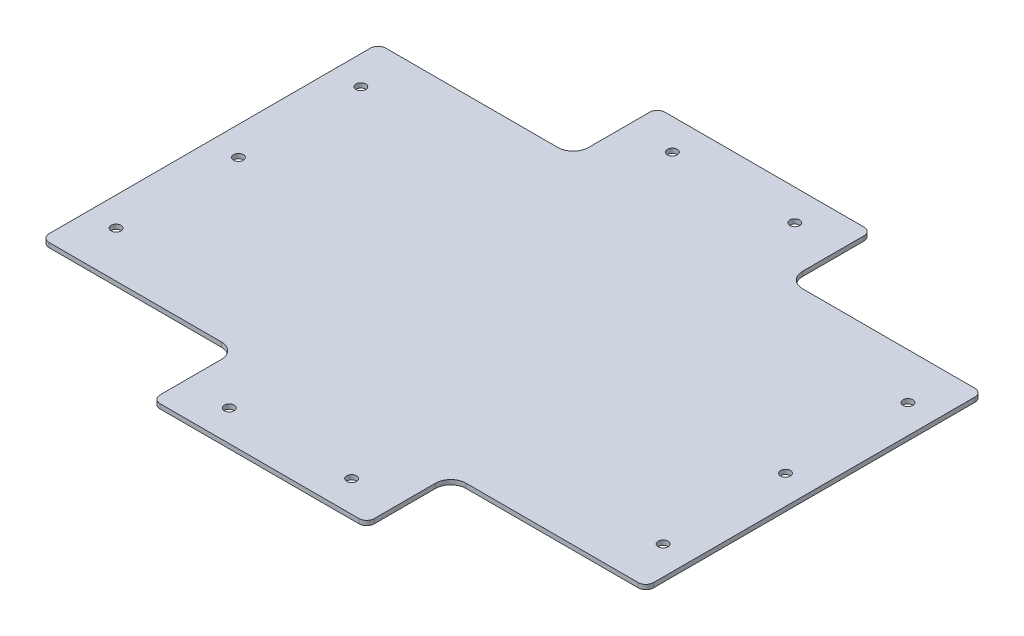
SolidWorks part; units mm, degrees
material "7075-T6, Пластина (SS)"
ref_plane "Спереди" through (0, 0, 0) normal (0, 0, 1) x (1, 0, 0)
ref_plane "Сверху" through (0, 0, 0) normal (0, 1, 0) x (1, 0, 0)
ref_plane "Справа" through (0, 0, 0) normal (1, 0, 0) x (0, 0, -1)
sketch "Эскиз1" plane through (0, 0, 0) normal (0, 1, 0) x (1, 0, 0)
  line L1 (-65, -165) -> (65, -165)
  line L2 (-197.5, -105) -> (-197.5, 105)
  line L3 (-65, 165) -> (65, 165)
  line L4 (197.5, -105) -> (197.5, 105)
  line L18 (-284.5497, 0) -> (284.3305, 0) construction
  line L19 (-160.9018, 110) -> (-134.9018, 110)
  line L39 (-70, 120) -> (-70, 160)
  line L40 (0, 262.7398) -> (0, -186.5795) construction
  line L41 (-192.5, 110) -> (-80, 110)
  line L43 (-192.5, -110) -> (-80, -110)
  line L44 (-70, -120) -> (-70, -160)
  line L45 (70, 120) -> (70, 160)
  line L46 (192.5, 110) -> (80, 110)
  line L47 (192.5, -110) -> (80, -110)
  line L48 (70, -120) -> (70, -160)
  line L54 (160.9018, -110) -> (134.9018, -110)
  line L60 (160.9018, 110) -> (134.9018, 110)
  line L65 (40, -144.8055) -> (-40, -144.8055) construction
  line L66 (-178.7687, -80) -> (-178.7687, 80) construction
  arc A0 (70, -120) -> (80, -110) centre (80, -120) cw
  arc A1 (70, 120) -> (80, 110) centre (80, 120) ccw
  arc A2 (-80, -110) -> (-70, -120) centre (-80, -120) cw
  arc A3 (-70, 120) -> (-80, 110) centre (-80, 120) cw
  arc A4 (192.5, -110) -> (197.5, -105) centre (192.5, -105) ccw
  arc A5 (70, -160) -> (65, -165) centre (65, -160) cw
  arc A6 (-70, -160) -> (-65, -165) centre (-65, -160) ccw
  arc A7 (-192.5, -110) -> (-197.5, -105) centre (-192.5, -105) cw
  arc A8 (-192.5, 110) -> (-197.5, 105) centre (-192.5, 105) ccw
  arc A9 (197.5, 105) -> (192.5, 110) centre (192.5, 105) ccw
  arc A10 (70, 160) -> (65, 165) centre (65, 160) ccw
  arc A11 (-70, 160) -> (-65, 165) centre (-65, 160) cw
  circle A12 centre (40, 144.8055) radius 3.2
  circle A13 centre (40, -144.8055) radius 3.2
  circle A14 centre (-40, -144.8055) radius 3.2
  circle A15 centre (-40, 144.8055) radius 3.2
  circle A16 centre (-178.7687, 80) radius 3.2
  circle A17 centre (-178.7687, -80) radius 3.2
  circle A18 centre (-178.7687, 0) radius 3.2
  circle A19 centre (178.7687, 80) radius 3.2
  circle A20 centre (178.7687, 0) radius 3.2
  circle A21 centre (178.7687, -80) radius 3.2
  point P0 (0, 0)
  point P3 (70, -110)
  point P17 (-147.9018, 110)
  point P18 (-147.9018, 110)
  point P46 (70, 110)
  point P52 (-70, -110)
  point P55 (-70, 110)
  point P56 (-147.9018, 0)
  point P59 (-178.7687, 0)
  point P62 (178.7687, 80)
  point P77 (197.5, -110)
  point P80 (70, -165)
  point P83 (-70, -165)
  point P86 (-197.5, -110)
  point P89 (-197.5, 110)
  point P92 (197.5, 110)
  point P95 (70, 165)
  point P98 (-70, 165)
  point P99 (178.7687, 0)
  point P100 (40, 144.8055)
  point P101 (178.7687, -80)
  point P103 (-40, 144.8055)
  dimension "D6" = 10
  dimension "D11" = 40
  dimension "D12" = 40
  dimension "D4" = 5
  dimension "D9" = 6.4
  dimension "D5" = 330
  dimension "D7" = 395
  dimension "D15" = 80
  dimension "D16" = 80
  dimension "D18" = 18.7313
  dimension "D19" = 20.1945
extrude "Бобышка-Вытянуть1" add sketch "Эскиз1" along normal blind 3 separate body contours A11 L39 A3 L41 L43 A2 L44 A6 L1 A5 L48 A0 L47 L46 A1 L45 A10 L3 | L4 A9 L46 L47 A4 | L46 | L47 | L41 A8 L2 A7 L43 | L19 region at (0, 0, 0)
sketch "линии симметрии" plane through (0, 3, 0) normal (0, 1, 0) x (1, 0, 0)
  line L0 (-197.5, 0) -> (197.5, 0)
  line L1 (-197.5, -105) -> (-197.5, 105) construction
  line L2 (197.5, -105) -> (197.5, 105) construction
  line L3 (0, 165) -> (0, -165)
  line L4 (-65, 165) -> (65, 165) construction
  line L5 (-65, -165) -> (65, -165) construction
